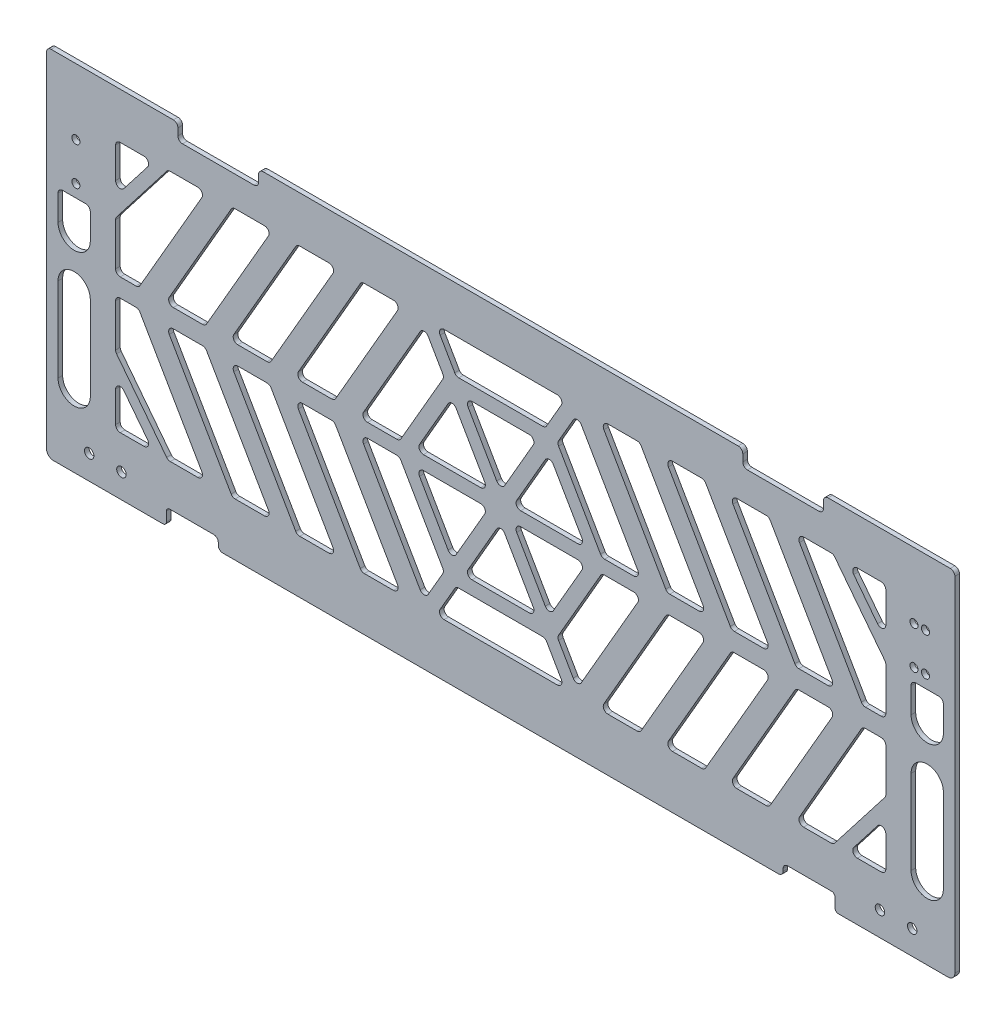
SolidWorks part; units mm, degrees
material "Thornel Mat VMA"
ref_plane "前视基准面" through (0, 0, 0) normal (0, 0, 1) x (1, 0, 0)
ref_plane "上视基准面" through (0, 0, 0) normal (0, 1, 0) x (1, 0, 0)
ref_plane "右视基准面" through (0, 0, 0) normal (1, 0, 0) x (0, 0, -1)
sketch "草图1" plane through (0, 0, 0) normal (0, 0, 1) x (1, 0, 0)
  line L1 (-197, -79.5) -> (197, -79.5)
  line L2 (-197, -79.5) -> (-197, 79.5)
  line L3 (-197, 79.5) -> (197, 79.5)
  line L4 (197, -79.5) -> (197, 79.5)
  line L5 (-197, -79.5) -> (197, 79.5) construction
  line L6 (-197, 79.5) -> (197, -79.5) construction
  point P0 (0, 0)
  dimension "D1" = 394
  dimension "D2" = 159
extrude "凸台-拉伸1" add sketch "草图1" along normal blind 2
sketch "草图2" plane through (0, 0, 2) normal (0, 0, 1) x (1, 0, 0)
  line L0 (197, 79.5) -> (-197, 79.5) construction
  line L1 (31.4656, 54.5) -> (-31.4656, 54.5)
  line L2 (-31.4656, 54.5) -> (-62.9312, 0)
  line L3 (-62.9312, 0) -> (-31.4656, -54.5)
  line L4 (-31.4656, -54.5) -> (31.4656, -54.5)
  line L5 (31.4656, -54.5) -> (62.9312, 0)
  line L6 (62.9312, 0) -> (31.4656, 54.5)
  line L7 (-31.4656, 54.5) -> (31.4656, -54.5) construction
  line L8 (31.4656, 54.5) -> (-31.4656, -54.5) construction
  line L9 (-62.9312, 0) -> (62.9312, 0) construction
  line L10 (-34.0637, 53) -> (28.8675, -56)
  line L11 (28.8675, 56) -> (-34.0637, -53)
  line L12 (-62.9312, -3) -> (62.9312, -3)
  line L13 (-28.8675, 56) -> (34.0637, -53)
  line L14 (34.0637, 53) -> (-28.8675, -56)
  line L15 (-62.9312, 3) -> (62.9312, 3)
  line L16 (197, -79.5) -> (197, 79.5) construction
  line L17 (197, 64.5) -> (-197, 64.5)
  line L18 (197, 64.5) -> (197, 79.5)
  line L19 (197, 79.5) -> (-197, 79.5)
  line L20 (-197, 64.5) -> (-197, 79.5)
  circle A0 centre (0, 0) radius 54.5 construction
  dimension "D1" = 25
  dimension "D4" = 15
  dimension "D2" = 3
  dimension "D3" = 3
extrude "切除-拉伸1" cut sketch "草图2" against normal blind 10 contours L10 L14 L4 | L12 L13 L5 | L14 L15 L6 | L1 L13 L11 | L2 L15 L10 | L12 L3 L11 region at (0, 38.3333, 2) region at (33.1976, 19.1667, 2) region at (-33.1976, 19.1667, 2) region at (33.1976, -19.1667, 2) region at (-33.1976, -19.1667, 2) region at (0, -38.3333, 2)
sketch "草图4" plane through (0, 0, 2) normal (0, 0, 1) x (1, 0, 0)
  line L4 (-22.8053, 39.5) -> (-45.6107, 0)
  line L5 (-45.6107, 0) -> (-22.8053, -39.5)
  line L6 (-22.8053, -39.5) -> (22.8053, -39.5)
  line L7 (22.8053, -39.5) -> (45.6107, 0)
  line L8 (45.6107, 0) -> (22.8053, 39.5)
  line L9 (22.8053, 39.5) -> (-22.8053, 39.5)
  line L10 (-28.0015, 54.5) -> (28.0015, 54.5) construction
  line L11 (-19.3412, 33.5) -> (-38.6825, 0)
  line L12 (-38.6825, 0) -> (-19.3412, -33.5)
  line L13 (-19.3412, -33.5) -> (19.3412, -33.5)
  line L14 (19.3412, -33.5) -> (38.6825, 0)
  line L15 (38.6825, 0) -> (19.3412, 33.5)
  line L16 (19.3412, 33.5) -> (-19.3412, 33.5)
  circle A1 centre (0, 0) radius 39.5 construction
  dimension "D1" = 15
  dimension "D2" = 6
extrude "凸台-拉伸2" add sketch "草图4" against normal up to surface (2 mm away) up to face at (0, 38.3333, 0)
sketch "草图5" plane through (0, 0, 0) normal (0, 0, -1) x (-1, 0, 0)
  line L0 (0, 0) -> (197, 0) construction
  line L1 (197, 79.5) -> (197, -79.5) construction
  line L2 (28.0015, 54.5) -> (197, 54.5)
  line L3 (43.0126, 54.5) -> (74.4782, 0)
  line L4 (61.1991, 3) -> (33.1976, 51.5) construction
  line L5 (60.3331, 54.5) -> (91.7987, 0)
  line L6 (88.3331, 54.5) -> (119.7987, 0)
  line L7 (71.0126, 54.5) -> (102.4782, 0)
  line L8 (116.3331, 54.5) -> (147.7987, 0)
  line L9 (99.0126, 54.5) -> (130.4782, 0)
  line L10 (60.3331, 54.5) -> (88.3331, 54.5) construction
  line L11 (99.0126, -54.5) -> (130.4782, 0)
  line L12 (116.3331, -54.5) -> (147.7987, 0)
  line L13 (71.0126, -54.5) -> (102.4782, 0)
  line L14 (88.3331, -54.5) -> (119.7987, 0)
  line L15 (60.3331, -54.5) -> (91.7987, 0)
  line L16 (43.0126, -54.5) -> (74.4782, 0)
  line L17 (43.0126, -54.5) -> (60.3331, -54.5)
  line L18 (71.0126, -54.5) -> (88.3331, -54.5)
  line L19 (99.0126, -54.5) -> (116.3331, -54.5)
  line L20 (0, -4) -> (197, -4)
  line L21 (0, 4) -> (197, 4)
  dimension "D1" = 10
  dimension "D2" = 15
  dimension "D4" = 28
  dimension "D5" = 4
  dimension "D6" = 4
  dimension "D3" = 3
extrude "切除-拉伸2" cut sketch "草图5" against normal blind 10 contours L3 L21 L5 L2 | L7 L21 L6 L2 | L9 L21 L8 L2 | L20 L11 L19 L12 | L20 L13 L18 L14 | L20 L16 L17 L15 region at (-66.2509, 29.25, 0) region at (-94.2509, 29.25, 0) region at (-66.2509, -29.25, 0) region at (-122.2509, 29.25, 0) region at (-94.2509, -29.25, 0) region at (-122.2509, -29.25, 0)
mirror "镜向1" about plane through (0, 0, 0) normal (1, 0, 0) of "切除-拉伸2"
fillet "圆角1" radius 3 4 edges at (197, -79.5, 1) (197, 79.5, 1) (-197, -79.5, 1) (-197, 79.5, 1)
sketch "草图6" plane through (0, 0, 2) normal (0, 0, 1) x (1, 0, 0)
  line L0 (127.8801, 54.5) -> (157.0363, 4)
  line L1 (157.0363, 4) -> (167.0363, 4)
  line L2 (167.0363, 4) -> (167.0363, 54.5)
  line L3 (167.0363, 54.5) -> (127.8801, 54.5)
  line L4 (99.0126, 54.5) -> (116.3331, 54.5) construction
  line L5 (116.3331, 54.5) -> (145.4893, 4) construction
  line L6 (128.1688, 4) -> (145.4893, 4) construction
  line L7 (0, 0) -> (213.285, 0) construction
  line L8 (167.0363, -54.5) -> (127.8801, -54.5)
  line L9 (167.0363, -4) -> (167.0363, -54.5)
  line L10 (157.0363, -4) -> (167.0363, -4)
  line L11 (127.8801, -54.5) -> (157.0363, -4)
  line L12 (0, 0) -> (0, 79.5) construction
  line L13 (194, 79.5) -> (-194, 79.5) construction
  line L14 (-167.0363, -4) -> (-167.0363, -54.5)
  line L15 (-157.0363, -4) -> (-167.0363, -4)
  line L16 (-127.8801, -54.5) -> (-157.0363, -4)
  line L17 (-167.0363, -54.5) -> (-127.8801, -54.5)
  line L18 (-167.0363, 4) -> (-167.0363, 54.5)
  line L19 (-157.0363, 4) -> (-167.0363, 4)
  line L20 (-127.8801, 54.5) -> (-157.0363, 4)
  line L21 (-167.0363, 54.5) -> (-127.8801, 54.5)
  dimension "D1" = 10
  dimension "D2" = 10
extrude "切除-拉伸3" cut sketch "草图6" against normal blind 10
sketch "草图7" plane through (0, 0, 2) normal (0, 0, 1) x (1, 0, 0)
  line L0 (147.4582, 54.5) -> (167.0363, 29.25) construction
  line L1 (167.0363, 54.5) -> (127.8801, 54.5) construction
  line L2 (167.0363, 4) -> (167.0363, 54.5) construction
  line L3 (144.2947, 54.5) -> (167.0363, 25.1701)
  line L4 (150.6217, 54.5) -> (169.012, 30.7819)
  line L5 (145.4825, 52.9681) -> (165.0606, 27.7181) construction
  line L6 (149.4339, 56.0319) -> (169.012, 30.7819) construction
  line L7 (169.012, 30.7819) -> (167.0363, 25.1701)
  line L8 (144.2947, 54.5) -> (150.6217, 54.5)
  line L9 (0, 0) -> (234.1972, 0) construction
  line L10 (147.4582, -54.5) -> (167.0363, -29.25) construction
  line L11 (144.2947, -54.5) -> (150.6217, -54.5)
  line L12 (169.012, -30.7819) -> (167.0363, -25.1701)
  line L13 (150.6217, -54.5) -> (169.012, -30.7819)
  line L14 (144.2947, -54.5) -> (167.0363, -25.1701)
  dimension "D1" = 2.5
  dimension "D2" = 2.5
extrude "凸台-拉伸3" add sketch "草图7" against normal up to surface (2 mm away) up to face at (-154.7472, 29.25, 0)
mirror "镜向2" about plane through (0, 0, 0) normal (1, 0, 0) of "凸台-拉伸3"
fillet "圆角2" radius 2 122 edges at (116.3331, 54.5, 1) (145.4893, 4, 1) (128.1688, 4, 1) (99.0126, 54.5, 1) (88.3331, 54.5, 1) (117.4893, 4, 1) (100.1688, 4, 1) (71.0126, 54.5, 1) (60.3331, 54.5, 1) (89.4893, 4, 1) (72.1688, 4, 1) (43.0126, 54.5, 1) (-71.0126, -54.5, 1) (-88.3331, -54.5, 1) (-117.4893, -4, 1) (-100.1688, -4, 1) (-99.0126, -54.5, 1) (-116.3331, -54.5, 1) (-145.4893, -4, 1) (-128.1688, -4, 1) (-43.0126, -54.5, 1) (-60.3331, -54.5, 1) (-89.4893, -4, 1) (-72.1688, -4, 1) (-21.0733, 30.5, 1) (-5.1962, 3, 1) (-36.9504, 3, 1) (-36.9504, -3, 1) (-5.1962, -3, 1) (-21.0733, -30.5, 1) (-15.8771, -33.5, 1) (0, -6, 1) (15.8771, -33.5, 1) (21.0733, -30.5, 1) (5.1962, -3, 1) (36.9504, -3, 1) (36.9504, 3, 1) (5.1962, 3, 1) (21.0733, 30.5, 1) (15.8771, 33.5, 1) (0, 6, 1) (-15.8771, 33.5, 1) (-61.1991, 3, 1) (-33.1976, 51.5, 1) (-24.5374, 36.5, 1) (-43.8786, 3, 1) (-33.1976, -51.5, 1) (-61.1991, -3, 1) (-43.8786, -3, 1) (-24.5374, -36.5, 1) (28.0015, -54.5, 1) (-28.0015, -54.5, 1) (-19.3412, -39.5, 1) (19.3412, -39.5, 1) (61.1991, -3, 1) (33.1976, -51.5, 1) (24.5374, -36.5, 1) (43.8786, -3, 1) (33.1976, 51.5, 1) (61.1991, 3, 1) (43.8786, 3, 1) (24.5374, 36.5, 1) (-28.0015, 54.5, 1) (28.0015, 54.5, 1) (19.3412, 39.5, 1) (-19.3412, 39.5, 1) (-72.1688, 4, 1) (-89.4893, 4, 1) (-60.3331, 54.5, 1) (-43.0126, 54.5, 1) (-100.1688, 4, 1) (-117.4893, 4, 1) (-88.3331, 54.5, 1) (-71.0126, 54.5, 1) (-128.1688, 4, 1) (-145.4893, 4, 1) (-116.3331, 54.5, 1) (-99.0126, 54.5, 1) (89.4893, -4, 1) (60.3331, -54.5, 1) (43.0126, -54.5, 1) (72.1688, -4, 1) (145.4893, -4, 1) (116.3331, -54.5, 1) (99.0126, -54.5, 1) (128.1688, -4, 1) (117.4893, -4, 1) (88.3331, -54.5, 1) (71.0126, -54.5, 1) (100.1688, -4, 1) (150.6217, 54.5, 1) (167.0363, 54.5, 1) (167.0363, 33.3299, 1) (127.8801, 54.5, 1) (144.2947, 54.5, 1) (167.0363, 25.1701, 1) (144.2947, -54.5, 1) (127.8801, -54.5, 1) (157.0363, -4, 1) (167.0363, -4, 1) (167.0363, -25.1701, 1) (167.0363, -54.5, 1) (150.6217, -54.5, 1) (167.0363, -33.3299, 1) (-167.0363, 54.5, 1) (-150.6217, 54.5, 1) (-167.0363, 33.3299, 1) (-144.2947, 54.5, 1) (-127.8801, 54.5, 1) (-157.0363, 4, 1) (-167.0363, 4, 1) (-167.0363, 25.1701, 1) (-167.0363, -4, 1) (-157.0363, -4, 1) (-127.8801, -54.5, 1) (-144.2947, -54.5, 1) (-167.0363, -25.1701, 1) (-150.6217, -54.5, 1) (-167.0363, -54.5, 1) (-167.0363, -33.3299, 1) (157.0363, 4, 1) (167.0363, 4, 1)
sketch "草图8" plane through (0, 0, 2) normal (0, 0, 1) x (1, 0, 0)
  line L0 (185, 47.5) -> (185, 11) construction
  line L1 (192, 47.5) -> (192, 11)
  line L2 (178, 47.5) -> (178, 11)
  line L3 (165.0363, 54.5) -> (154.7032, 54.5) construction
  line L4 (158.191, 4) -> (165.0363, 4) construction
  line L5 (197, -76.5) -> (197, 76.5) construction
  line L6 (0, 0) -> (235.1793, 0) construction
  line L7 (185, -47.5) -> (185, -11) construction
  line L8 (192, -47.5) -> (192, -11)
  line L9 (178, -47.5) -> (178, -11)
  arc A0 (192, 47.5) -> (178, 47.5) centre (185, 47.5) ccw
  arc A1 (178, 11) -> (192, 11) centre (185, 11) ccw
  arc A2 (192, -47.5) -> (178, -47.5) centre (185, -47.5) cw
  arc A3 (178, -11) -> (192, -11) centre (185, -11) cw
  point P2 (185, 29.25)
  point P18 (185, -29.25)
  dimension "D2" = 7
  dimension "D1" = 5
extrude "切除-拉伸4" cut sketch "草图8" against normal blind 10
mirror "镜向3" about plane through (0, 0, 0) normal (1, 0, 0) of "切除-拉伸4"
sketch "草图9" plane through (0, 0, 2) normal (0, 0, 1) x (1, 0, 0)
  line L2 (-145, -79.5) -> (145, -79.5)
  line L4 (-145, -79.5) -> (-145, -72.5)
  line L5 (-194, -79.5) -> (194, -79.5) construction
  line L6 (-145, -72.5) -> (145, -72.5)
  line L7 (0, 0) -> (0, -72.5) construction
  line L8 (145, -79.5) -> (145, -72.5)
  point P12 (0, -79.5)
  dimension "D1" = 7
  dimension "D2" = 145
extrude "切除-拉伸5" cut sketch "草图9" against normal blind 10
sketch "草图10" plane through (0, 0, 2) normal (0, 0, 1) x (1, 0, 0)
  line L0 (194, 79.5) -> (-194, 79.5) construction
  line L1 (-20, 59.5) -> (20, 59.5)
  line L2 (-20, 59.5) -> (-20, 74.5)
  line L3 (-20, 74.5) -> (20, 74.5)
  line L4 (20, 59.5) -> (20, 74.5)
  line L5 (-20, 59.5) -> (20, 74.5) construction
  line L6 (-20, 74.5) -> (20, 59.5) construction
  line L7 (24.5374, 54.5) -> (-24.5374, 54.5) construction
  line L8 (0, 67) -> (0, 0) construction
  point P0 (0, 67)
  dimension "D1" = 5
  dimension "D2" = 5
  dimension "D3" = 40
extrude "切除-拉伸6" [suppressed] cut sketch "草图10" against normal blind 10
pattern_linear "阵列(线性)1" [suppressed] count 4 spacing 54 count 4 spacing 54 of bodies 117
fillet "圆角3" [suppressed] radius 3
sketch "草图12" plane through (0, 0, 2) normal (0, 0, 1) x (1, 0, 0)
  line L0 (178.5, -69) -> (164.5, -69) construction
  line L1 (164.5, -69) -> (0, -69) construction
  line L3 (0, -69) -> (0, 0) construction
  line L4 (145, -79.5) -> (194, -79.5) construction
  line L5 (197, -76.5) -> (197, 76.5) construction
  circle A2 centre (164.5, -69) radius 2.05
  circle A3 centre (178.5, -69) radius 2.05
  dimension "D4" = 10.5
  dimension "D6" = 4.1
  dimension "D1" = 69
  dimension "D2" = 164.5
  dimension "D3" = 14
  dimension "D5" = 18.5
extrude "切除-拉伸8" cut sketch "草图12" against normal blind 10
mirror "镜向5" about plane through (0, 0, 0) normal (1, 0, 0) of "切除-拉伸8"
fillet "圆角4" radius 1.5 4 edges at (145, -79.5, 1) (145, -72.5, 1) (-145, -79.5, 1) (-145, -72.5, 1)
sketch "草图13" plane through (0, 0, 2) normal (0, 0, 1) x (1, 0, 0)
  line L0 (143.5, -72.5) -> (-143.5, -72.5) construction
  line L1 (-122.5, -77.5) -> (122.5, -77.5)
  line L2 (-122.5, -77.5) -> (-122.5, -67.5)
  line L3 (-122.5, -67.5) -> (122.5, -67.5)
  line L4 (122.5, -77.5) -> (122.5, -67.5)
  line L5 (0, -67.5) -> (0, -77.5) construction
  line L6 (-122.5, -72.5) -> (122.5, -72.5) construction
  point P0 (0, -72.5)
  dimension "D1" = 5
  dimension "D2" = 245
extrude "凸台-拉伸4" add sketch "草图13" against normal up to surface (2 mm away) up to face at (-166.55, -69, 0)
fillet "圆角5" radius 2 4 edges at (122.5, -77.5, 1) (122.5, -72.5, 1) (-122.5, -77.5, 1) (-122.5, -72.5, 1)
sketch "草图14" plane through (0, 0, 2) normal (0, 0, 1) x (1, 0, 0)
  line L0 (-192, 24) -> (-178, 24)
  line L1 (-192, 11) -> (-192, 47.5) construction
  line L2 (-178, 47.5) -> (-178, 11) construction
  line L3 (-178, 24) -> (-178, 47.5)
  line L4 (-192, 47.5) -> (-192, 24)
  line L5 (0, 0) -> (0, 105.1212) construction
  line L6 (192, 47.5) -> (192, 24)
  line L7 (178, 24) -> (178, 47.5)
  line L8 (192, 24) -> (178, 24)
  arc A0 (-178, 47.5) -> (-192, 47.5) centre (-185, 47.5) ccw construction
  arc A1 (-178, 47.5) -> (-192, 47.5) centre (-185, 47.5) ccw
  arc A2 (178, 47.5) -> (192, 47.5) centre (185, 47.5) cw
  dimension "D1" = 24
extrude "凸台-拉伸5" add sketch "草图14" against normal up to surface (2 mm away) up to face at (0, -50.3333, 0)
sketch "草图15" plane through (0, 0, 2) normal (0, 0, 1) x (1, 0, 0)
  line L0 (0, 0) -> (0, -145.7941) construction
  circle A0 centre (-184.25, 45.925) radius 1.75 construction
  circle A1 centre (-184.25, 29.425) radius 1.75 construction
  circle A2 centre (-184.25, 45.925) radius 1.75
  circle A3 centre (-184.25, 29.425) radius 1.75
  circle A4 centre (184.25, 29.425) radius 1.75
  circle A5 centre (184.25, 45.925) radius 1.75
extrude "切除-拉伸9" cut sketch "草图15" against normal blind 10
fillet "圆角6" radius 2 4 edges at (-192, 24, 1) (-178, 24, 1) (192, 24, 1) (178, 24, 1)
sketch "草图16" plane through (0, 0, 2) normal (0, 0, 1) x (1, 0, 0)
  line L0 (197, -76.5) -> (197, 76.5) construction
  line L1 (197, 74.5) -> (-197, 74.5)
  line L2 (197, 74.5) -> (197, 79.5)
  line L3 (197, 79.5) -> (-197, 79.5)
  line L4 (-197, 74.5) -> (-197, 79.5)
  line L5 (-197, 76.5) -> (-197, -76.5) construction
  line L6 (194, 79.5) -> (-194, 79.5) construction
  dimension "D1" = 5
extrude "切除-拉伸10" cut sketch "草图16" against normal blind 10
fillet "圆角7" radius 2 2 edges at (-197, 74.5, 1) (197, 74.5, 1)
sketch "草图17" plane through (0, 0, 2) normal (0, 0, 1) x (1, 0, 0)
  line L0 (-195, 74.5) -> (195, 74.5) construction
  line L1 (140, 74.5) -> (105, 74.5)
  line L2 (140, 74.5) -> (140, 67.5)
  line L3 (140, 67.5) -> (105, 67.5)
  line L4 (105, 74.5) -> (105, 67.5)
  line L5 (197, -76.5) -> (197, 72.5) construction
  line L6 (0, 0) -> (0, -108.5128) construction
  line L7 (-105, 74.5) -> (-105, 67.5)
  line L8 (-140, 67.5) -> (-105, 67.5)
  line L9 (-140, 74.5) -> (-140, 67.5)
  line L10 (-140, 74.5) -> (-105, 74.5)
  dimension "D1" = 35
  dimension "D2" = 7
  dimension "D3" = 57
extrude "切除-拉伸11" cut sketch "草图17" against normal blind 10
fillet "圆角8" radius 2 8 edges at (140, 67.5, 1) (105, 67.5, 1) (105, 74.5, 1) (-105, 74.5, 1) (-105, 67.5, 1) (-140, 67.5, 1) (-140, 74.5, 1) (140, 74.5, 1)
sketch "草图18" plane through (0, 0, 0) normal (0, 0, -1) x (-1, 0, 0)
  circle A0 centre (-179.25, 45.925) radius 1.75
  circle A1 centre (-179.25, 29.425) radius 1.75
  circle A2 centre (-184.25, 29.425) radius 1.75 construction
  circle A3 centre (-184.25, 45.925) radius 1.75 construction
  circle A4 centre (-184.25, 29.425) radius 1.75
  circle A5 centre (-184.25, 45.925) radius 1.75
  dimension "D1" = 5
extrude "切除-拉伸12" cut sketch "草图18" against normal blind 10
